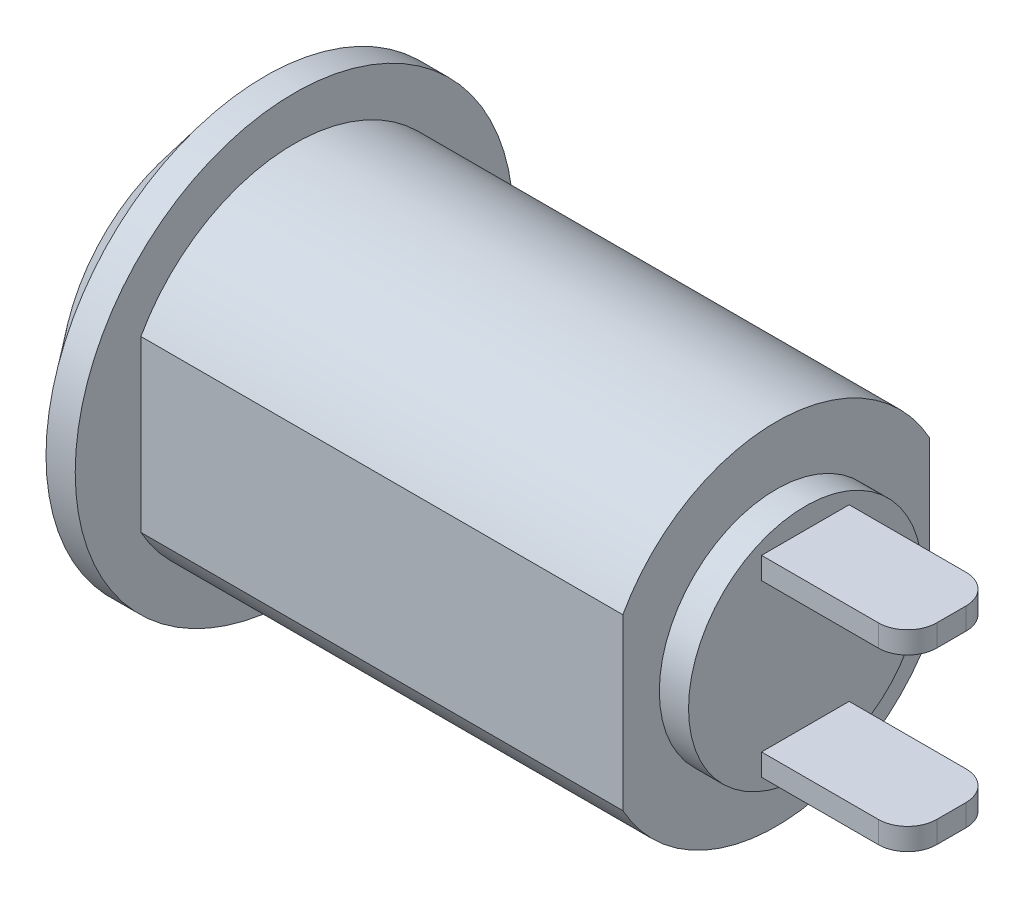
SolidWorks part; units mm, degrees
ref_plane "前视基准面" through (0, 0, 0) normal (0, 0, 1) x (1, 0, 0)
ref_plane "上视基准面" through (0, 0, 0) normal (0, 1, 0) x (1, 0, 0)
ref_plane "右视基准面" through (0, 0, 0) normal (1, 0, 0) x (0, 0, -1)
sketch "草图1" plane through (0, 0, 0) normal (0, 0, 1) x (1, 0, 0)
  line L0 (0, 0) -> (25.1904, 0) construction
  line L1 (0, 0) -> (0, 5)
  line L2 (0, 5) -> (2, 7.5)
  line L3 (2, 7.5) -> (3, 7.5)
  line L4 (3, 7.5) -> (3, 6)
  line L5 (3, 6) -> (19.5, 6)
  line L6 (19.5, 6) -> (19.5, 4)
  line L7 (19.5, 4) -> (20.5, 4)
  line L8 (20.5, 4) -> (20.5, 0)
  line L9 (0, 0) -> (20.5, 0)
  dimension "D1" = 3
  dimension "D2" = 16.5
  dimension "D3" = 1
  dimension "D4" = 6
  dimension "D5" = 7.5
  dimension "D6" = 5
  dimension "D7" = 2
  dimension "D8" = 4
revolve "旋转1" add sketch "草图1" angle 360 about L0
sketch "草图2" plane through (0, 0, 0) normal (1, 0, 0) x (0, 0, -1)
  line L0 (3.341, 0) -> (-2.9465, 0) construction
  line L1 (1, 3.25) -> (-1, 3.25)
  line L2 (1, 3.25) -> (1, -3.25)
  line L3 (1, -3.25) -> (-1, -3.25)
  line L4 (-1, 3.25) -> (-1, -3.25)
  line L5 (0, 3.7355) -> (0, -4.6232) construction
  dimension "D1" = 2
  dimension "D2" = 6.5
extrude "切除-拉伸1" cut sketch "草图2" along normal blind 10
sketch "草图3" plane through (20.5, 0, 0) normal (1, 0, 0) x (0, 0, -1)
  line L0 (0, 12.0791) -> (0, -13.3573) construction
  line L1 (-11.0019, 9.8635) -> (-5.25, 9.8635)
  line L2 (-11.0019, 9.8635) -> (-11.0019, -8.5853)
  line L3 (-11.0019, -8.5853) -> (-5.25, -8.5853)
  line L4 (-5.25, 9.8635) -> (-5.25, -8.5853)
  line L5 (5.25, 9.8635) -> (5.25, -8.5853)
  line L6 (11.0019, -8.5853) -> (5.25, -8.5853)
  line L7 (11.0019, 9.8635) -> (11.0019, -8.5853)
  line L8 (11.0019, 9.8635) -> (5.25, 9.8635)
  dimension "D1" = 10.5
extrude "切除-拉伸2" cut sketch "草图3" against normal up to surface (17.5 mm away) up to face at (3, 0, 7.5)
sketch "草图4" plane through (20.5, 0, 0) normal (1, 0, 0) x (0, 0, -1)
  line L0 (-9.5052, 0) -> (9.9737, 0) construction
  line L1 (0, 7.9765) -> (0, -8.5189) construction
  line L2 (-1.5, 3.29) -> (1.5, 3.29)
  line L3 (-1.5, 3.29) -> (-1.5, 2.54)
  line L4 (-1.5, 2.54) -> (1.5, 2.54)
  line L5 (1.5, 3.29) -> (1.5, 2.54)
  line L6 (1.5, -3.29) -> (1.5, -2.54)
  line L7 (-1.5, -2.54) -> (1.5, -2.54)
  line L8 (-1.5, -3.29) -> (-1.5, -2.54)
  line L9 (-1.5, -3.29) -> (1.5, -3.29)
  dimension "D1" = 0.75
  dimension "D2" = 3
  dimension "D3" = 5.08
extrude "凸台-拉伸2" add sketch "草图4" along normal blind 5
fillet "圆角1" radius 1 4 edges at (25.5, -2.915, -1.5) (25.5, -2.915, 1.5) (25.5, 2.915, 1.5) (25.5, 2.915, -1.5)
